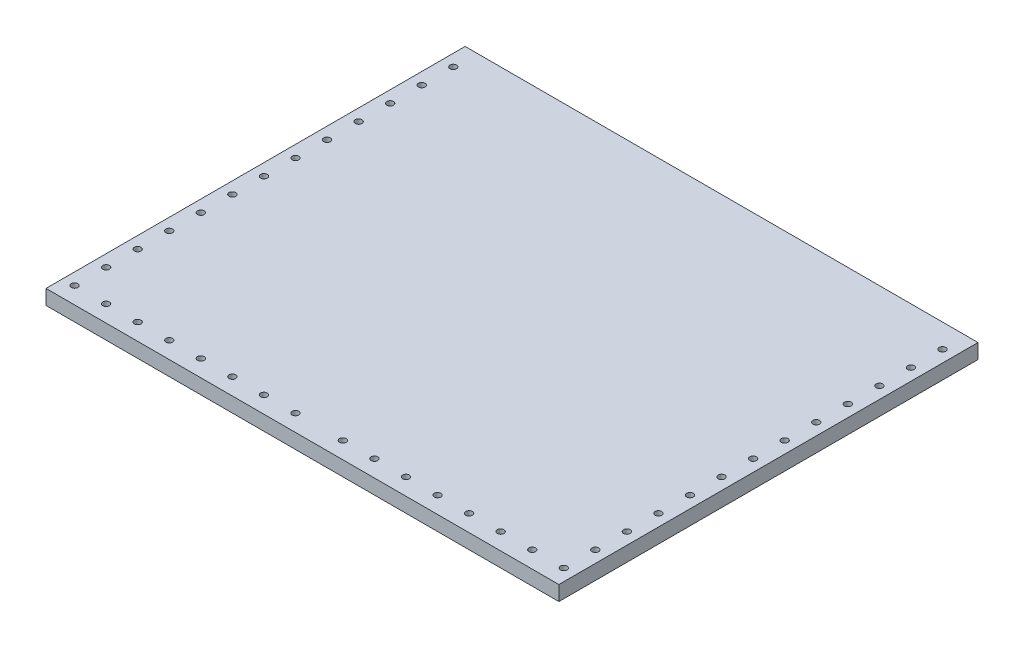
SolidWorks part; units mm, degrees
material "Teak"
ref_plane "Front Plane" through (0, 0, 0) normal (0, 0, 1) x (1, 0, 0)
ref_plane "Top Plane" through (0, 0, 0) normal (0, 1, 0) x (1, 0, 0)
ref_plane "Right Plane" through (0, 0, 0) normal (1, 0, 0) x (0, 0, -1)
sketch "Sketch1" plane through (0, 0, 0) normal (0, 1, 0) x (1, 0, 0)
  line L1 (0, 0) -> (412.75, 0)
  line L2 (0, 0) -> (0, 584.2)
  line L3 (0, 584.2) -> (412.75, 584.2)
  line L4 (412.75, 0) -> (412.75, 584.2)
  dimension "D1" = 584.2
  dimension "D2" = 412.75
extrude "Boss-Extrude1" add sketch "Sketch1" along normal blind 11.9062
sketch "Sketch2" plane through (0, 11.9062, 0) normal (0, 1, 0) x (1, 0, 0)
  line L0 (0, 584.2) -> (0, 0) construction
  line L1 (0, 477.012) -> (40.64, 477.012)
  line L2 (0, 477.012) -> (0, 337.312)
  line L3 (0, 337.312) -> (40.64, 337.312)
  line L4 (40.64, 477.012) -> (40.64, 337.312)
  line L5 (206.375, 0) -> (206.375, 59.5989)
  line L7 (0, 0) -> (412.75, 0) construction
  line L8 (372.11, 477.012) -> (372.11, 337.312)
  line L9 (412.75, 337.312) -> (372.11, 337.312)
  line L10 (412.75, 477.012) -> (412.75, 337.312)
  line L11 (412.75, 477.012) -> (372.11, 477.012)
  line M5 (0, 584.2) -> (0, 0)
  line M7 (412.75, 0) -> (412.75, 584.2)
  dimension "D1" = 139.7
  dimension "D2" = 40.64
extrude "Cut-Extrude1" cut sketch "Sketch2" against normal through all contours L4 L1 L3 M5 | L11 L8 L9 M7 region at (20.32, 11.9062, -407.162) region at (392.43, 11.9062, -407.162)
sketch "Sketch3" plane through (0, 11.9062, 0) normal (0, 1, 0) x (1, 0, 0)
  line L0 (0, 337.312) -> (0, 0) construction
  line L1 (0, 0) -> (412.75, 0) construction
  circle A0 centre (9.525, 13.462) radius 2.667
  circle A2 centre (34.925, 13.462) radius 2.667
  circle A4 centre (60.325, 13.462) radius 2.667
  circle A6 centre (85.725, 13.462) radius 2.667
  circle A8 centre (111.125, 13.462) radius 2.667
  circle A10 centre (136.525, 13.462) radius 2.667
  circle A12 centre (161.925, 13.462) radius 2.667
  circle A14 centre (187.325, 13.462) radius 2.667
  circle A17 centre (225.425, 13.462) radius 2.667
  circle A19 centre (250.825, 13.462) radius 2.667
  circle A21 centre (276.225, 13.462) radius 2.667
  circle A23 centre (301.625, 13.462) radius 2.667
  circle A25 centre (327.025, 13.462) radius 2.667
  circle A27 centre (352.425, 13.462) radius 2.667
  circle A29 centre (377.825, 13.462) radius 2.667
  circle A31 centre (403.225, 13.462) radius 2.667
  circle A62 centre (403.225, 38.862) radius 2.667
  circle A93 centre (403.225, 64.262) radius 2.667
  circle A124 centre (403.225, 89.662) radius 2.667
  circle A155 centre (403.225, 115.062) radius 2.667
  circle A186 centre (403.225, 140.462) radius 2.667
  circle A217 centre (403.225, 165.862) radius 2.667
  circle A248 centre (403.225, 191.262) radius 2.667
  circle A279 centre (403.225, 216.662) radius 2.667
  circle A310 centre (403.225, 242.062) radius 2.667
  circle A341 centre (403.225, 267.462) radius 2.667
  circle A372 centre (403.225, 292.862) radius 2.667
  circle A403 centre (403.225, 318.262) radius 2.667
  circle A434 centre (403.225, 343.662) radius 2.667
  circle A465 centre (403.225, 369.062) radius 2.667
  circle A496 centre (403.225, 394.462) radius 2.667
  circle A527 centre (403.225, 419.862) radius 2.667
  circle A558 centre (403.225, 445.262) radius 2.667
  circle A589 centre (403.225, 470.662) radius 2.667
  circle A620 centre (403.225, 496.062) radius 2.667
  circle A651 centre (403.225, 521.462) radius 2.667
  circle A682 centre (403.225, 546.862) radius 2.667
  circle A713 centre (403.225, 572.262) radius 2.667
  circle A714 centre (9.525, 38.862) radius 2.667
  circle A715 centre (9.525, 64.262) radius 2.667
  circle A716 centre (9.525, 89.662) radius 2.667
  circle A717 centre (9.525, 115.062) radius 2.667
  circle A718 centre (9.525, 140.462) radius 2.667
  circle A719 centre (9.525, 165.862) radius 2.667
  circle A720 centre (9.525, 191.262) radius 2.667
  circle A721 centre (9.525, 216.662) radius 2.667
  circle A722 centre (9.525, 242.062) radius 2.667
  circle A723 centre (9.525, 267.462) radius 2.667
  circle A724 centre (9.525, 292.862) radius 2.667
  circle A725 centre (9.525, 318.262) radius 2.667
  circle A726 centre (9.525, 343.662) radius 2.667
  circle A727 centre (9.525, 369.062) radius 2.667
  circle A728 centre (9.525, 394.462) radius 2.667
  circle A729 centre (9.525, 419.862) radius 2.667
  circle A730 centre (9.525, 445.262) radius 2.667
  circle A731 centre (9.525, 470.662) radius 2.667
  circle A732 centre (9.525, 496.062) radius 2.667
  circle A733 centre (9.525, 521.462) radius 2.667
  circle A734 centre (9.525, 546.862) radius 2.667
  circle A735 centre (9.525, 572.262) radius 2.667
  circle A736 centre (34.925, 38.862) radius 2.667 [skipped]
  circle A737 centre (47.625, 38.862) radius 2.667 [skipped]
  circle A738 centre (60.325, 38.862) radius 2.667 [skipped]
  circle A739 centre (73.025, 38.862) radius 2.667 [skipped]
  circle A740 centre (85.725, 38.862) radius 2.667 [skipped]
  circle A741 centre (98.425, 38.862) radius 2.667 [skipped]
  circle A742 centre (111.125, 38.862) radius 2.667 [skipped]
  circle A743 centre (123.825, 38.862) radius 2.667 [skipped]
  circle A744 centre (136.525, 38.862) radius 2.667 [skipped]
  circle A745 centre (149.225, 38.862) radius 2.667 [skipped]
  circle A746 centre (161.925, 38.862) radius 2.667 [skipped]
  circle A747 centre (174.625, 38.862) radius 2.667 [skipped]
  circle A748 centre (187.325, 38.862) radius 2.667 [skipped]
  circle A749 centre (200.025, 38.862) radius 2.667 [skipped]
  circle A750 centre (212.725, 38.862) radius 2.667 [skipped]
  circle A751 centre (225.425, 38.862) radius 2.667 [skipped]
  circle A752 centre (238.125, 38.862) radius 2.667 [skipped]
  circle A753 centre (250.825, 38.862) radius 2.667 [skipped]
  circle A754 centre (263.525, 38.862) radius 2.667 [skipped]
  circle A755 centre (276.225, 38.862) radius 2.667 [skipped]
  circle A756 centre (288.925, 38.862) radius 2.667 [skipped]
  circle A757 centre (301.625, 38.862) radius 2.667 [skipped]
  circle A758 centre (314.325, 38.862) radius 2.667 [skipped]
  circle A759 centre (327.025, 38.862) radius 2.667 [skipped]
  circle A760 centre (339.725, 38.862) radius 2.667 [skipped]
  circle A761 centre (352.425, 38.862) radius 2.667 [skipped]
  circle A762 centre (365.125, 38.862) radius 2.667 [skipped]
  circle A763 centre (377.825, 38.862) radius 2.667 [skipped]
  circle A764 centre (390.525, 38.862) radius 2.667 [skipped]
  circle A765 centre (34.925, 64.262) radius 2.667 [skipped]
  circle A766 centre (47.625, 64.262) radius 2.667 [skipped]
  circle A767 centre (60.325, 64.262) radius 2.667 [skipped]
  circle A768 centre (73.025, 64.262) radius 2.667 [skipped]
  circle A769 centre (85.725, 64.262) radius 2.667 [skipped]
  circle A770 centre (98.425, 64.262) radius 2.667 [skipped]
  circle A771 centre (111.125, 64.262) radius 2.667 [skipped]
  circle A772 centre (123.825, 64.262) radius 2.667 [skipped]
  circle A773 centre (136.525, 64.262) radius 2.667 [skipped]
  circle A774 centre (149.225, 64.262) radius 2.667 [skipped]
  circle A775 centre (161.925, 64.262) radius 2.667 [skipped]
  circle A776 centre (174.625, 64.262) radius 2.667 [skipped]
  circle A777 centre (187.325, 64.262) radius 2.667 [skipped]
  circle A778 centre (200.025, 64.262) radius 2.667 [skipped]
  circle A779 centre (212.725, 64.262) radius 2.667 [skipped]
  circle A780 centre (225.425, 64.262) radius 2.667 [skipped]
  circle A781 centre (238.125, 64.262) radius 2.667 [skipped]
  circle A782 centre (250.825, 64.262) radius 2.667 [skipped]
  circle A783 centre (263.525, 64.262) radius 2.667 [skipped]
  circle A784 centre (276.225, 64.262) radius 2.667 [skipped]
  circle A785 centre (288.925, 64.262) radius 2.667 [skipped]
  circle A786 centre (301.625, 64.262) radius 2.667 [skipped]
  circle A787 centre (314.325, 64.262) radius 2.667 [skipped]
  circle A788 centre (327.025, 64.262) radius 2.667 [skipped]
  circle A789 centre (339.725, 64.262) radius 2.667 [skipped]
  circle A790 centre (352.425, 64.262) radius 2.667 [skipped]
  circle A791 centre (365.125, 64.262) radius 2.667 [skipped]
  circle A792 centre (377.825, 64.262) radius 2.667 [skipped]
  circle A793 centre (390.525, 64.262) radius 2.667 [skipped]
  circle A794 centre (34.925, 89.662) radius 2.667 [skipped]
  circle A795 centre (47.625, 89.662) radius 2.667 [skipped]
  circle A796 centre (60.325, 89.662) radius 2.667 [skipped]
  circle A797 centre (73.025, 89.662) radius 2.667 [skipped]
  circle A798 centre (85.725, 89.662) radius 2.667 [skipped]
  circle A799 centre (98.425, 89.662) radius 2.667 [skipped]
  circle A800 centre (111.125, 89.662) radius 2.667 [skipped]
  circle A801 centre (123.825, 89.662) radius 2.667 [skipped]
  circle A802 centre (136.525, 89.662) radius 2.667 [skipped]
  circle A803 centre (149.225, 89.662) radius 2.667 [skipped]
  circle A804 centre (161.925, 89.662) radius 2.667 [skipped]
  circle A805 centre (174.625, 89.662) radius 2.667 [skipped]
  circle A806 centre (187.325, 89.662) radius 2.667 [skipped]
  circle A807 centre (200.025, 89.662) radius 2.667 [skipped]
  circle A808 centre (212.725, 89.662) radius 2.667 [skipped]
  circle A809 centre (225.425, 89.662) radius 2.667 [skipped]
  circle A810 centre (238.125, 89.662) radius 2.667 [skipped]
  circle A811 centre (250.825, 89.662) radius 2.667 [skipped]
  circle A812 centre (263.525, 89.662) radius 2.667 [skipped]
  circle A813 centre (276.225, 89.662) radius 2.667 [skipped]
  circle A814 centre (288.925, 89.662) radius 2.667 [skipped]
  circle A815 centre (301.625, 89.662) radius 2.667 [skipped]
  circle A816 centre (314.325, 89.662) radius 2.667 [skipped]
  circle A817 centre (327.025, 89.662) radius 2.667 [skipped]
  circle A818 centre (339.725, 89.662) radius 2.667 [skipped]
  circle A819 centre (352.425, 89.662) radius 2.667 [skipped]
  circle A820 centre (365.125, 89.662) radius 2.667 [skipped]
  circle A821 centre (377.825, 89.662) radius 2.667 [skipped]
  circle A822 centre (390.525, 89.662) radius 2.667 [skipped]
  circle A823 centre (34.925, 115.062) radius 2.667 [skipped]
  circle A824 centre (47.625, 115.062) radius 2.667 [skipped]
  circle A825 centre (60.325, 115.062) radius 2.667 [skipped]
  circle A826 centre (73.025, 115.062) radius 2.667 [skipped]
  circle A827 centre (85.725, 115.062) radius 2.667 [skipped]
  circle A828 centre (98.425, 115.062) radius 2.667 [skipped]
  circle A829 centre (111.125, 115.062) radius 2.667 [skipped]
  circle A830 centre (123.825, 115.062) radius 2.667 [skipped]
  circle A831 centre (136.525, 115.062) radius 2.667 [skipped]
  circle A832 centre (149.225, 115.062) radius 2.667 [skipped]
  circle A833 centre (161.925, 115.062) radius 2.667 [skipped]
  circle A834 centre (174.625, 115.062) radius 2.667 [skipped]
  circle A835 centre (187.325, 115.062) radius 2.667 [skipped]
  circle A836 centre (200.025, 115.062) radius 2.667 [skipped]
  circle A837 centre (212.725, 115.062) radius 2.667 [skipped]
  circle A838 centre (225.425, 115.062) radius 2.667 [skipped]
  circle A839 centre (238.125, 115.062) radius 2.667 [skipped]
  circle A840 centre (250.825, 115.062) radius 2.667 [skipped]
  circle A841 centre (263.525, 115.062) radius 2.667 [skipped]
  circle A842 centre (276.225, 115.062) radius 2.667 [skipped]
  circle A843 centre (288.925, 115.062) radius 2.667 [skipped]
  circle A844 centre (301.625, 115.062) radius 2.667 [skipped]
  circle A845 centre (314.325, 115.062) radius 2.667 [skipped]
  circle A846 centre (327.025, 115.062) radius 2.667 [skipped]
  circle A847 centre (339.725, 115.062) radius 2.667 [skipped]
  circle A848 centre (352.425, 115.062) radius 2.667 [skipped]
  circle A849 centre (365.125, 115.062) radius 2.667 [skipped]
  circle A850 centre (377.825, 115.062) radius 2.667 [skipped]
  circle A851 centre (390.525, 115.062) radius 2.667 [skipped]
  circle A852 centre (34.925, 140.462) radius 2.667 [skipped]
  circle A853 centre (47.625, 140.462) radius 2.667 [skipped]
  circle A854 centre (60.325, 140.462) radius 2.667 [skipped]
  circle A855 centre (73.025, 140.462) radius 2.667 [skipped]
  circle A856 centre (85.725, 140.462) radius 2.667 [skipped]
  circle A857 centre (98.425, 140.462) radius 2.667 [skipped]
  circle A858 centre (111.125, 140.462) radius 2.667 [skipped]
  circle A859 centre (123.825, 140.462) radius 2.667 [skipped]
  circle A860 centre (136.525, 140.462) radius 2.667 [skipped]
  circle A861 centre (149.225, 140.462) radius 2.667 [skipped]
  circle A862 centre (161.925, 140.462) radius 2.667 [skipped]
  circle A863 centre (174.625, 140.462) radius 2.667 [skipped]
  circle A864 centre (187.325, 140.462) radius 2.667 [skipped]
  circle A865 centre (200.025, 140.462) radius 2.667 [skipped]
  circle A866 centre (212.725, 140.462) radius 2.667 [skipped]
  circle A867 centre (225.425, 140.462) radius 2.667 [skipped]
  circle A868 centre (238.125, 140.462) radius 2.667 [skipped]
  circle A869 centre (250.825, 140.462) radius 2.667 [skipped]
  circle A870 centre (263.525, 140.462) radius 2.667 [skipped]
  circle A871 centre (276.225, 140.462) radius 2.667 [skipped]
  circle A872 centre (288.925, 140.462) radius 2.667 [skipped]
  circle A873 centre (301.625, 140.462) radius 2.667 [skipped]
  circle A874 centre (314.325, 140.462) radius 2.667 [skipped]
  circle A875 centre (327.025, 140.462) radius 2.667 [skipped]
  circle A876 centre (339.725, 140.462) radius 2.667 [skipped]
  circle A877 centre (352.425, 140.462) radius 2.667 [skipped]
  circle A878 centre (365.125, 140.462) radius 2.667 [skipped]
  circle A879 centre (377.825, 140.462) radius 2.667 [skipped]
  circle A880 centre (390.525, 140.462) radius 2.667 [skipped]
  circle A881 centre (34.925, 165.862) radius 2.667 [skipped]
  circle A882 centre (47.625, 165.862) radius 2.667 [skipped]
  circle A883 centre (60.325, 165.862) radius 2.667 [skipped]
  circle A884 centre (73.025, 165.862) radius 2.667 [skipped]
  circle A885 centre (85.725, 165.862) radius 2.667 [skipped]
  circle A886 centre (98.425, 165.862) radius 2.667 [skipped]
  circle A887 centre (111.125, 165.862) radius 2.667 [skipped]
  circle A888 centre (123.825, 165.862) radius 2.667 [skipped]
  circle A889 centre (136.525, 165.862) radius 2.667 [skipped]
  circle A890 centre (149.225, 165.862) radius 2.667 [skipped]
  circle A891 centre (161.925, 165.862) radius 2.667 [skipped]
  circle A892 centre (174.625, 165.862) radius 2.667 [skipped]
  circle A893 centre (187.325, 165.862) radius 2.667 [skipped]
  circle A894 centre (200.025, 165.862) radius 2.667 [skipped]
  circle A895 centre (212.725, 165.862) radius 2.667 [skipped]
  circle A896 centre (225.425, 165.862) radius 2.667 [skipped]
  circle A897 centre (238.125, 165.862) radius 2.667 [skipped]
  circle A898 centre (250.825, 165.862) radius 2.667 [skipped]
  circle A899 centre (263.525, 165.862) radius 2.667 [skipped]
  circle A900 centre (276.225, 165.862) radius 2.667 [skipped]
  circle A901 centre (288.925, 165.862) radius 2.667 [skipped]
  circle A902 centre (301.625, 165.862) radius 2.667 [skipped]
  circle A903 centre (314.325, 165.862) radius 2.667 [skipped]
  circle A904 centre (327.025, 165.862) radius 2.667 [skipped]
  circle A905 centre (339.725, 165.862) radius 2.667 [skipped]
  circle A906 centre (352.425, 165.862) radius 2.667 [skipped]
  circle A907 centre (365.125, 165.862) radius 2.667 [skipped]
  circle A908 centre (377.825, 165.862) radius 2.667 [skipped]
  circle A909 centre (390.525, 165.862) radius 2.667 [skipped]
  circle A910 centre (34.925, 191.262) radius 2.667 [skipped]
  circle A911 centre (47.625, 191.262) radius 2.667 [skipped]
  circle A912 centre (60.325, 191.262) radius 2.667 [skipped]
  circle A913 centre (73.025, 191.262) radius 2.667 [skipped]
  circle A914 centre (85.725, 191.262) radius 2.667 [skipped]
  circle A915 centre (98.425, 191.262) radius 2.667 [skipped]
  circle A916 centre (111.125, 191.262) radius 2.667 [skipped]
  circle A917 centre (123.825, 191.262) radius 2.667 [skipped]
  circle A918 centre (136.525, 191.262) radius 2.667 [skipped]
  circle A919 centre (149.225, 191.262) radius 2.667 [skipped]
  circle A920 centre (161.925, 191.262) radius 2.667 [skipped]
  circle A921 centre (174.625, 191.262) radius 2.667 [skipped]
  circle A922 centre (187.325, 191.262) radius 2.667 [skipped]
  circle A923 centre (200.025, 191.262) radius 2.667 [skipped]
  circle A924 centre (212.725, 191.262) radius 2.667 [skipped]
  circle A925 centre (225.425, 191.262) radius 2.667 [skipped]
  circle A926 centre (238.125, 191.262) radius 2.667 [skipped]
  circle A927 centre (250.825, 191.262) radius 2.667 [skipped]
  circle A928 centre (263.525, 191.262) radius 2.667 [skipped]
  circle A929 centre (276.225, 191.262) radius 2.667 [skipped]
  circle A930 centre (288.925, 191.262) radius 2.667 [skipped]
  circle A931 centre (301.625, 191.262) radius 2.667 [skipped]
  circle A932 centre (314.325, 191.262) radius 2.667 [skipped]
  circle A933 centre (327.025, 191.262) radius 2.667 [skipped]
  circle A934 centre (339.725, 191.262) radius 2.667 [skipped]
  circle A935 centre (352.425, 191.262) radius 2.667 [skipped]
  circle A936 centre (365.125, 191.262) radius 2.667 [skipped]
  circle A937 centre (377.825, 191.262) radius 2.667 [skipped]
  circle A938 centre (390.525, 191.262) radius 2.667 [skipped]
  circle A939 centre (34.925, 216.662) radius 2.667 [skipped]
  circle A940 centre (47.625, 216.662) radius 2.667 [skipped]
  circle A941 centre (60.325, 216.662) radius 2.667 [skipped]
  circle A942 centre (73.025, 216.662) radius 2.667 [skipped]
  circle A943 centre (85.725, 216.662) radius 2.667 [skipped]
  circle A944 centre (98.425, 216.662) radius 2.667 [skipped]
  circle A945 centre (111.125, 216.662) radius 2.667 [skipped]
  circle A946 centre (123.825, 216.662) radius 2.667 [skipped]
  circle A947 centre (136.525, 216.662) radius 2.667 [skipped]
  circle A948 centre (149.225, 216.662) radius 2.667 [skipped]
  circle A949 centre (161.925, 216.662) radius 2.667 [skipped]
  circle A950 centre (174.625, 216.662) radius 2.667 [skipped]
  circle A951 centre (187.325, 216.662) radius 2.667 [skipped]
  circle A952 centre (200.025, 216.662) radius 2.667 [skipped]
  circle A953 centre (212.725, 216.662) radius 2.667 [skipped]
  circle A954 centre (225.425, 216.662) radius 2.667 [skipped]
  circle A955 centre (238.125, 216.662) radius 2.667 [skipped]
  circle A956 centre (250.825, 216.662) radius 2.667 [skipped]
  circle A957 centre (263.525, 216.662) radius 2.667 [skipped]
  circle A958 centre (276.225, 216.662) radius 2.667 [skipped]
  circle A959 centre (288.925, 216.662) radius 2.667 [skipped]
  circle A960 centre (301.625, 216.662) radius 2.667 [skipped]
  circle A961 centre (314.325, 216.662) radius 2.667 [skipped]
  circle A962 centre (327.025, 216.662) radius 2.667 [skipped]
  circle A963 centre (339.725, 216.662) radius 2.667 [skipped]
  circle A964 centre (352.425, 216.662) radius 2.667 [skipped]
  circle A965 centre (365.125, 216.662) radius 2.667 [skipped]
  circle A966 centre (377.825, 216.662) radius 2.667 [skipped]
  circle A967 centre (390.525, 216.662) radius 2.667 [skipped]
  circle A968 centre (34.925, 242.062) radius 2.667 [skipped]
  circle A969 centre (47.625, 242.062) radius 2.667 [skipped]
  circle A970 centre (60.325, 242.062) radius 2.667 [skipped]
  circle A971 centre (73.025, 242.062) radius 2.667 [skipped]
  circle A972 centre (85.725, 242.062) radius 2.667 [skipped]
  circle A973 centre (98.425, 242.062) radius 2.667 [skipped]
  circle A974 centre (111.125, 242.062) radius 2.667 [skipped]
  circle A975 centre (123.825, 242.062) radius 2.667 [skipped]
  circle A976 centre (136.525, 242.062) radius 2.667 [skipped]
  circle A977 centre (149.225, 242.062) radius 2.667 [skipped]
  circle A978 centre (161.925, 242.062) radius 2.667 [skipped]
  circle A979 centre (174.625, 242.062) radius 2.667 [skipped]
  circle A980 centre (187.325, 242.062) radius 2.667 [skipped]
  circle A981 centre (200.025, 242.062) radius 2.667 [skipped]
  circle A982 centre (212.725, 242.062) radius 2.667 [skipped]
  circle A983 centre (225.425, 242.062) radius 2.667 [skipped]
  circle A984 centre (238.125, 242.062) radius 2.667 [skipped]
  circle A985 centre (250.825, 242.062) radius 2.667 [skipped]
  circle A986 centre (263.525, 242.062) radius 2.667 [skipped]
  circle A987 centre (276.225, 242.062) radius 2.667 [skipped]
  circle A988 centre (288.925, 242.062) radius 2.667 [skipped]
  circle A989 centre (301.625, 242.062) radius 2.667 [skipped]
  circle A990 centre (314.325, 242.062) radius 2.667 [skipped]
  circle A991 centre (327.025, 242.062) radius 2.667 [skipped]
  circle A992 centre (339.725, 242.062) radius 2.667 [skipped]
  circle A993 centre (352.425, 242.062) radius 2.667 [skipped]
  circle A994 centre (365.125, 242.062) radius 2.667 [skipped]
  circle A995 centre (377.825, 242.062) radius 2.667 [skipped]
  circle A996 centre (390.525, 242.062) radius 2.667 [skipped]
  circle A997 centre (34.925, 267.462) radius 2.667 [skipped]
  circle A998 centre (47.625, 267.462) radius 2.667 [skipped]
  circle A999 centre (60.325, 267.462) radius 2.667 [skipped]
  circle A1000 centre (73.025, 267.462) radius 2.667 [skipped]
  circle A1001 centre (85.725, 267.462) radius 2.667 [skipped]
  circle A1002 centre (98.425, 267.462) radius 2.667 [skipped]
  circle A1003 centre (111.125, 267.462) radius 2.667 [skipped]
  circle A1004 centre (123.825, 267.462) radius 2.667 [skipped]
  circle A1005 centre (136.525, 267.462) radius 2.667 [skipped]
  circle A1006 centre (149.225, 267.462) radius 2.667 [skipped]
  circle A1007 centre (161.925, 267.462) radius 2.667 [skipped]
  circle A1008 centre (174.625, 267.462) radius 2.667 [skipped]
  circle A1009 centre (187.325, 267.462) radius 2.667 [skipped]
  circle A1010 centre (200.025, 267.462) radius 2.667 [skipped]
  circle A1011 centre (212.725, 267.462) radius 2.667 [skipped]
  circle A1012 centre (225.425, 267.462) radius 2.667 [skipped]
  circle A1013 centre (238.125, 267.462) radius 2.667 [skipped]
  circle A1014 centre (250.825, 267.462) radius 2.667 [skipped]
  circle A1015 centre (263.525, 267.462) radius 2.667 [skipped]
  circle A1016 centre (276.225, 267.462) radius 2.667 [skipped]
  circle A1017 centre (288.925, 267.462) radius 2.667 [skipped]
  circle A1018 centre (301.625, 267.462) radius 2.667 [skipped]
  circle A1019 centre (314.325, 267.462) radius 2.667 [skipped]
  circle A1020 centre (327.025, 267.462) radius 2.667 [skipped]
  circle A1021 centre (339.725, 267.462) radius 2.667 [skipped]
  circle A1022 centre (352.425, 267.462) radius 2.667 [skipped]
  circle A1023 centre (365.125, 267.462) radius 2.667 [skipped]
  circle A1024 centre (377.825, 267.462) radius 2.667 [skipped]
  circle A1025 centre (390.525, 267.462) radius 2.667 [skipped]
  circle A1026 centre (34.925, 292.862) radius 2.667 [skipped]
  circle A1027 centre (47.625, 292.862) radius 2.667 [skipped]
  circle A1028 centre (60.325, 292.862) radius 2.667 [skipped]
  circle A1029 centre (73.025, 292.862) radius 2.667 [skipped]
  circle A1030 centre (85.725, 292.862) radius 2.667 [skipped]
  circle A1031 centre (98.425, 292.862) radius 2.667 [skipped]
  circle A1032 centre (111.125, 292.862) radius 2.667 [skipped]
  circle A1033 centre (123.825, 292.862) radius 2.667 [skipped]
  circle A1034 centre (136.525, 292.862) radius 2.667 [skipped]
  circle A1035 centre (149.225, 292.862) radius 2.667 [skipped]
  circle A1036 centre (161.925, 292.862) radius 2.667 [skipped]
  circle A1037 centre (174.625, 292.862) radius 2.667 [skipped]
  circle A1038 centre (187.325, 292.862) radius 2.667 [skipped]
  circle A1039 centre (200.025, 292.862) radius 2.667 [skipped]
  circle A1040 centre (212.725, 292.862) radius 2.667 [skipped]
  circle A1041 centre (225.425, 292.862) radius 2.667 [skipped]
  circle A1042 centre (238.125, 292.862) radius 2.667 [skipped]
  circle A1043 centre (250.825, 292.862) radius 2.667 [skipped]
  circle A1044 centre (263.525, 292.862) radius 2.667 [skipped]
  circle A1045 centre (276.225, 292.862) radius 2.667 [skipped]
  circle A1046 centre (288.925, 292.862) radius 2.667 [skipped]
  circle A1047 centre (301.625, 292.862) radius 2.667 [skipped]
  circle A1048 centre (314.325, 292.862) radius 2.667 [skipped]
  circle A1049 centre (327.025, 292.862) radius 2.667 [skipped]
  circle A1050 centre (339.725, 292.862) radius 2.667 [skipped]
  circle A1051 centre (352.425, 292.862) radius 2.667 [skipped]
  circle A1052 centre (365.125, 292.862) radius 2.667 [skipped]
  circle A1053 centre (377.825, 292.862) radius 2.667 [skipped]
  circle A1054 centre (390.525, 292.862) radius 2.667 [skipped]
  circle A1055 centre (34.925, 318.262) radius 2.667 [skipped]
  circle A1056 centre (47.625, 318.262) radius 2.667 [skipped]
  circle A1057 centre (60.325, 318.262) radius 2.667 [skipped]
  circle A1058 centre (73.025, 318.262) radius 2.667 [skipped]
  circle A1059 centre (85.725, 318.262) radius 2.667 [skipped]
  circle A1060 centre (98.425, 318.262) radius 2.667 [skipped]
  circle A1061 centre (111.125, 318.262) radius 2.667 [skipped]
  circle A1062 centre (123.825, 318.262) radius 2.667 [skipped]
  circle A1063 centre (136.525, 318.262) radius 2.667 [skipped]
  circle A1064 centre (149.225, 318.262) radius 2.667 [skipped]
  circle A1065 centre (161.925, 318.262) radius 2.667 [skipped]
  circle A1066 centre (174.625, 318.262) radius 2.667 [skipped]
  circle A1067 centre (187.325, 318.262) radius 2.667 [skipped]
  circle A1068 centre (200.025, 318.262) radius 2.667 [skipped]
  circle A1069 centre (212.725, 318.262) radius 2.667 [skipped]
  circle A1070 centre (225.425, 318.262) radius 2.667 [skipped]
  circle A1071 centre (238.125, 318.262) radius 2.667 [skipped]
  circle A1072 centre (250.825, 318.262) radius 2.667 [skipped]
  circle A1073 centre (263.525, 318.262) radius 2.667 [skipped]
  circle A1074 centre (276.225, 318.262) radius 2.667 [skipped]
  circle A1075 centre (288.925, 318.262) radius 2.667 [skipped]
  circle A1076 centre (301.625, 318.262) radius 2.667 [skipped]
  circle A1077 centre (314.325, 318.262) radius 2.667 [skipped]
  circle A1078 centre (327.025, 318.262) radius 2.667 [skipped]
  circle A1079 centre (339.725, 318.262) radius 2.667 [skipped]
  circle A1080 centre (352.425, 318.262) radius 2.667 [skipped]
  circle A1081 centre (365.125, 318.262) radius 2.667 [skipped]
  circle A1082 centre (377.825, 318.262) radius 2.667 [skipped]
  circle A1083 centre (390.525, 318.262) radius 2.667 [skipped]
  circle A1084 centre (34.925, 343.662) radius 2.667 [skipped]
  circle A1085 centre (47.625, 343.662) radius 2.667 [skipped]
  circle A1086 centre (60.325, 343.662) radius 2.667 [skipped]
  circle A1087 centre (73.025, 343.662) radius 2.667 [skipped]
  circle A1088 centre (85.725, 343.662) radius 2.667 [skipped]
  circle A1089 centre (98.425, 343.662) radius 2.667 [skipped]
  circle A1090 centre (111.125, 343.662) radius 2.667 [skipped]
  circle A1091 centre (123.825, 343.662) radius 2.667 [skipped]
  circle A1092 centre (136.525, 343.662) radius 2.667 [skipped]
  circle A1093 centre (149.225, 343.662) radius 2.667 [skipped]
  circle A1094 centre (161.925, 343.662) radius 2.667 [skipped]
  circle A1095 centre (174.625, 343.662) radius 2.667 [skipped]
  circle A1096 centre (187.325, 343.662) radius 2.667 [skipped]
  circle A1097 centre (200.025, 343.662) radius 2.667 [skipped]
  circle A1098 centre (212.725, 343.662) radius 2.667 [skipped]
  circle A1099 centre (225.425, 343.662) radius 2.667 [skipped]
  circle A1100 centre (238.125, 343.662) radius 2.667 [skipped]
  circle A1101 centre (250.825, 343.662) radius 2.667 [skipped]
  circle A1102 centre (263.525, 343.662) radius 2.667 [skipped]
  circle A1103 centre (276.225, 343.662) radius 2.667 [skipped]
  circle A1104 centre (288.925, 343.662) radius 2.667 [skipped]
  circle A1105 centre (301.625, 343.662) radius 2.667 [skipped]
  circle A1106 centre (314.325, 343.662) radius 2.667 [skipped]
  circle A1107 centre (327.025, 343.662) radius 2.667 [skipped]
  circle A1108 centre (339.725, 343.662) radius 2.667 [skipped]
  circle A1109 centre (352.425, 343.662) radius 2.667 [skipped]
  circle A1110 centre (365.125, 343.662) radius 2.667 [skipped]
  circle A1111 centre (377.825, 343.662) radius 2.667 [skipped]
  circle A1112 centre (390.525, 343.662) radius 2.667 [skipped]
  circle A1113 centre (34.925, 369.062) radius 2.667 [skipped]
  circle A1114 centre (47.625, 369.062) radius 2.667 [skipped]
  circle A1115 centre (60.325, 369.062) radius 2.667 [skipped]
  circle A1116 centre (73.025, 369.062) radius 2.667 [skipped]
  circle A1117 centre (85.725, 369.062) radius 2.667 [skipped]
  circle A1118 centre (98.425, 369.062) radius 2.667 [skipped]
  circle A1119 centre (111.125, 369.062) radius 2.667 [skipped]
  circle A1120 centre (123.825, 369.062) radius 2.667 [skipped]
  circle A1121 centre (136.525, 369.062) radius 2.667 [skipped]
  circle A1122 centre (149.225, 369.062) radius 2.667 [skipped]
  circle A1123 centre (161.925, 369.062) radius 2.667 [skipped]
  circle A1124 centre (174.625, 369.062) radius 2.667 [skipped]
  circle A1125 centre (187.325, 369.062) radius 2.667 [skipped]
  circle A1126 centre (200.025, 369.062) radius 2.667 [skipped]
  circle A1127 centre (212.725, 369.062) radius 2.667 [skipped]
  circle A1128 centre (225.425, 369.062) radius 2.667 [skipped]
  circle A1129 centre (238.125, 369.062) radius 2.667 [skipped]
  circle A1130 centre (250.825, 369.062) radius 2.667 [skipped]
  circle A1131 centre (263.525, 369.062) radius 2.667 [skipped]
  circle A1132 centre (276.225, 369.062) radius 2.667 [skipped]
  circle A1133 centre (288.925, 369.062) radius 2.667 [skipped]
  circle A1134 centre (301.625, 369.062) radius 2.667 [skipped]
  circle A1135 centre (314.325, 369.062) radius 2.667 [skipped]
  circle A1136 centre (327.025, 369.062) radius 2.667 [skipped]
  circle A1137 centre (339.725, 369.062) radius 2.667 [skipped]
  circle A1138 centre (352.425, 369.062) radius 2.667 [skipped]
  circle A1139 centre (365.125, 369.062) radius 2.667 [skipped]
  circle A1140 centre (377.825, 369.062) radius 2.667 [skipped]
  circle A1141 centre (390.525, 369.062) radius 2.667 [skipped]
  circle A1142 centre (34.925, 394.462) radius 2.667 [skipped]
  circle A1143 centre (47.625, 394.462) radius 2.667 [skipped]
  circle A1144 centre (60.325, 394.462) radius 2.667 [skipped]
  circle A1145 centre (73.025, 394.462) radius 2.667 [skipped]
  circle A1146 centre (85.725, 394.462) radius 2.667 [skipped]
  circle A1147 centre (98.425, 394.462) radius 2.667 [skipped]
  circle A1148 centre (111.125, 394.462) radius 2.667 [skipped]
  circle A1149 centre (123.825, 394.462) radius 2.667 [skipped]
  circle A1150 centre (136.525, 394.462) radius 2.667 [skipped]
  circle A1151 centre (149.225, 394.462) radius 2.667 [skipped]
  circle A1152 centre (161.925, 394.462) radius 2.667 [skipped]
  circle A1153 centre (174.625, 394.462) radius 2.667 [skipped]
  circle A1154 centre (187.325, 394.462) radius 2.667 [skipped]
  circle A1155 centre (200.025, 394.462) radius 2.667 [skipped]
  circle A1156 centre (212.725, 394.462) radius 2.667 [skipped]
  circle A1157 centre (225.425, 394.462) radius 2.667 [skipped]
  circle A1158 centre (238.125, 394.462) radius 2.667 [skipped]
  circle A1159 centre (250.825, 394.462) radius 2.667 [skipped]
  circle A1160 centre (263.525, 394.462) radius 2.667 [skipped]
  circle A1161 centre (276.225, 394.462) radius 2.667 [skipped]
  circle A1162 centre (288.925, 394.462) radius 2.667 [skipped]
  circle A1163 centre (301.625, 394.462) radius 2.667 [skipped]
  circle A1164 centre (314.325, 394.462) radius 2.667 [skipped]
  circle A1165 centre (327.025, 394.462) radius 2.667 [skipped]
  circle A1166 centre (339.725, 394.462) radius 2.667 [skipped]
  circle A1167 centre (352.425, 394.462) radius 2.667 [skipped]
  circle A1168 centre (365.125, 394.462) radius 2.667 [skipped]
  circle A1169 centre (377.825, 394.462) radius 2.667 [skipped]
  circle A1170 centre (390.525, 394.462) radius 2.667 [skipped]
  circle A1171 centre (34.925, 419.862) radius 2.667 [skipped]
  circle A1172 centre (47.625, 419.862) radius 2.667 [skipped]
  circle A1173 centre (60.325, 419.862) radius 2.667 [skipped]
  circle A1174 centre (73.025, 419.862) radius 2.667 [skipped]
  circle A1175 centre (85.725, 419.862) radius 2.667 [skipped]
  circle A1176 centre (98.425, 419.862) radius 2.667 [skipped]
  circle A1177 centre (111.125, 419.862) radius 2.667 [skipped]
  circle A1178 centre (123.825, 419.862) radius 2.667 [skipped]
  circle A1179 centre (136.525, 419.862) radius 2.667 [skipped]
  circle A1180 centre (149.225, 419.862) radius 2.667 [skipped]
  circle A1181 centre (161.925, 419.862) radius 2.667 [skipped]
  circle A1182 centre (174.625, 419.862) radius 2.667 [skipped]
  circle A1183 centre (187.325, 419.862) radius 2.667 [skipped]
  circle A1184 centre (200.025, 419.862) radius 2.667 [skipped]
  circle A1185 centre (212.725, 419.862) radius 2.667 [skipped]
  circle A1186 centre (225.425, 419.862) radius 2.667 [skipped]
  circle A1187 centre (238.125, 419.862) radius 2.667 [skipped]
  circle A1188 centre (250.825, 419.862) radius 2.667 [skipped]
  circle A1189 centre (263.525, 419.862) radius 2.667 [skipped]
  circle A1190 centre (276.225, 419.862) radius 2.667 [skipped]
  circle A1191 centre (288.925, 419.862) radius 2.667 [skipped]
  circle A1192 centre (301.625, 419.862) radius 2.667 [skipped]
  circle A1193 centre (314.325, 419.862) radius 2.667 [skipped]
  circle A1194 centre (327.025, 419.862) radius 2.667 [skipped]
  circle A1195 centre (339.725, 419.862) radius 2.667 [skipped]
  circle A1196 centre (352.425, 419.862) radius 2.667 [skipped]
  circle A1197 centre (365.125, 419.862) radius 2.667 [skipped]
  circle A1198 centre (377.825, 419.862) radius 2.667 [skipped]
  circle A1199 centre (390.525, 419.862) radius 2.667 [skipped]
  circle A1200 centre (34.925, 445.262) radius 2.667 [skipped]
  circle A1201 centre (47.625, 445.262) radius 2.667 [skipped]
  circle A1202 centre (60.325, 445.262) radius 2.667 [skipped]
  circle A1203 centre (73.025, 445.262) radius 2.667 [skipped]
  circle A1204 centre (85.725, 445.262) radius 2.667 [skipped]
  circle A1205 centre (98.425, 445.262) radius 2.667 [skipped]
  circle A1206 centre (111.125, 445.262) radius 2.667 [skipped]
  circle A1207 centre (123.825, 445.262) radius 2.667 [skipped]
  circle A1208 centre (136.525, 445.262) radius 2.667 [skipped]
  circle A1209 centre (149.225, 445.262) radius 2.667 [skipped]
  circle A1210 centre (161.925, 445.262) radius 2.667 [skipped]
  circle A1211 centre (174.625, 445.262) radius 2.667 [skipped]
  circle A1212 centre (187.325, 445.262) radius 2.667 [skipped]
  circle A1213 centre (200.025, 445.262) radius 2.667 [skipped]
  circle A1214 centre (212.725, 445.262) radius 2.667 [skipped]
  circle A1215 centre (225.425, 445.262) radius 2.667 [skipped]
  circle A1216 centre (238.125, 445.262) radius 2.667 [skipped]
  circle A1217 centre (250.825, 445.262) radius 2.667 [skipped]
  circle A1218 centre (263.525, 445.262) radius 2.667 [skipped]
  circle A1219 centre (276.225, 445.262) radius 2.667 [skipped]
  circle A1220 centre (288.925, 445.262) radius 2.667 [skipped]
  circle A1221 centre (301.625, 445.262) radius 2.667 [skipped]
  circle A1222 centre (314.325, 445.262) radius 2.667 [skipped]
  circle A1223 centre (327.025, 445.262) radius 2.667 [skipped]
  circle A1224 centre (339.725, 445.262) radius 2.667 [skipped]
  circle A1225 centre (352.425, 445.262) radius 2.667 [skipped]
  circle A1226 centre (365.125, 445.262) radius 2.667 [skipped]
  circle A1227 centre (377.825, 445.262) radius 2.667 [skipped]
  circle A1228 centre (390.525, 445.262) radius 2.667 [skipped]
  circle A1229 centre (34.925, 470.662) radius 2.667 [skipped]
  circle A1230 centre (47.625, 470.662) radius 2.667 [skipped]
  circle A1231 centre (60.325, 470.662) radius 2.667 [skipped]
  circle A1232 centre (73.025, 470.662) radius 2.667 [skipped]
  circle A1233 centre (85.725, 470.662) radius 2.667 [skipped]
  circle A1234 centre (98.425, 470.662) radius 2.667 [skipped]
  circle A1235 centre (111.125, 470.662) radius 2.667 [skipped]
  circle A1236 centre (123.825, 470.662) radius 2.667 [skipped]
  circle A1237 centre (136.525, 470.662) radius 2.667 [skipped]
  circle A1238 centre (149.225, 470.662) radius 2.667 [skipped]
  circle A1239 centre (161.925, 470.662) radius 2.667 [skipped]
  circle A1240 centre (174.625, 470.662) radius 2.667 [skipped]
  circle A1241 centre (187.325, 470.662) radius 2.667 [skipped]
  circle A1242 centre (200.025, 470.662) radius 2.667 [skipped]
  circle A1243 centre (212.725, 470.662) radius 2.667 [skipped]
  circle A1244 centre (225.425, 470.662) radius 2.667 [skipped]
  circle A1245 centre (238.125, 470.662) radius 2.667 [skipped]
  circle A1246 centre (250.825, 470.662) radius 2.667 [skipped]
  circle A1247 centre (263.525, 470.662) radius 2.667 [skipped]
  circle A1248 centre (276.225, 470.662) radius 2.667 [skipped]
  circle A1249 centre (288.925, 470.662) radius 2.667 [skipped]
  circle A1250 centre (301.625, 470.662) radius 2.667 [skipped]
  circle A1251 centre (314.325, 470.662) radius 2.667 [skipped]
  circle A1252 centre (327.025, 470.662) radius 2.667 [skipped]
  circle A1253 centre (339.725, 470.662) radius 2.667 [skipped]
  circle A1254 centre (352.425, 470.662) radius 2.667 [skipped]
  circle A1255 centre (365.125, 470.662) radius 2.667 [skipped]
  circle A1256 centre (377.825, 470.662) radius 2.667 [skipped]
  circle A1257 centre (390.525, 470.662) radius 2.667 [skipped]
  circle A1258 centre (34.925, 496.062) radius 2.667 [skipped]
  circle A1259 centre (47.625, 496.062) radius 2.667 [skipped]
  circle A1260 centre (60.325, 496.062) radius 2.667 [skipped]
  circle A1261 centre (73.025, 496.062) radius 2.667 [skipped]
  circle A1262 centre (85.725, 496.062) radius 2.667 [skipped]
  circle A1263 centre (98.425, 496.062) radius 2.667 [skipped]
  circle A1264 centre (111.125, 496.062) radius 2.667 [skipped]
  circle A1265 centre (123.825, 496.062) radius 2.667 [skipped]
  circle A1266 centre (136.525, 496.062) radius 2.667 [skipped]
  circle A1267 centre (149.225, 496.062) radius 2.667 [skipped]
  circle A1268 centre (161.925, 496.062) radius 2.667 [skipped]
  circle A1269 centre (174.625, 496.062) radius 2.667 [skipped]
  circle A1270 centre (187.325, 496.062) radius 2.667 [skipped]
  circle A1271 centre (200.025, 496.062) radius 2.667 [skipped]
  circle A1272 centre (212.725, 496.062) radius 2.667 [skipped]
  circle A1273 centre (225.425, 496.062) radius 2.667 [skipped]
  circle A1274 centre (238.125, 496.062) radius 2.667 [skipped]
  circle A1275 centre (250.825, 496.062) radius 2.667 [skipped]
  circle A1276 centre (263.525, 496.062) radius 2.667 [skipped]
  circle A1277 centre (276.225, 496.062) radius 2.667 [skipped]
  circle A1278 centre (288.925, 496.062) radius 2.667 [skipped]
  circle A1279 centre (301.625, 496.062) radius 2.667 [skipped]
  circle A1280 centre (314.325, 496.062) radius 2.667 [skipped]
  circle A1281 centre (327.025, 496.062) radius 2.667 [skipped]
  circle A1282 centre (339.725, 496.062) radius 2.667 [skipped]
  circle A1283 centre (352.425, 496.062) radius 2.667 [skipped]
  circle A1284 centre (365.125, 496.062) radius 2.667 [skipped]
  circle A1285 centre (377.825, 496.062) radius 2.667 [skipped]
  circle A1286 centre (390.525, 496.062) radius 2.667 [skipped]
  circle A1287 centre (34.925, 521.462) radius 2.667 [skipped]
  circle A1288 centre (47.625, 521.462) radius 2.667 [skipped]
  circle A1289 centre (60.325, 521.462) radius 2.667 [skipped]
  circle A1290 centre (73.025, 521.462) radius 2.667 [skipped]
  circle A1291 centre (85.725, 521.462) radius 2.667 [skipped]
  circle A1292 centre (98.425, 521.462) radius 2.667 [skipped]
  circle A1293 centre (111.125, 521.462) radius 2.667 [skipped]
  circle A1294 centre (123.825, 521.462) radius 2.667 [skipped]
  circle A1295 centre (136.525, 521.462) radius 2.667 [skipped]
  circle A1296 centre (149.225, 521.462) radius 2.667 [skipped]
  circle A1297 centre (161.925, 521.462) radius 2.667 [skipped]
  circle A1298 centre (174.625, 521.462) radius 2.667 [skipped]
  circle A1299 centre (187.325, 521.462) radius 2.667 [skipped]
  circle A1300 centre (200.025, 521.462) radius 2.667 [skipped]
  circle A1301 centre (212.725, 521.462) radius 2.667 [skipped]
  circle A1302 centre (225.425, 521.462) radius 2.667 [skipped]
  circle A1303 centre (238.125, 521.462) radius 2.667 [skipped]
  circle A1304 centre (250.825, 521.462) radius 2.667 [skipped]
  circle A1305 centre (263.525, 521.462) radius 2.667 [skipped]
  circle A1306 centre (276.225, 521.462) radius 2.667 [skipped]
  circle A1307 centre (288.925, 521.462) radius 2.667 [skipped]
  circle A1308 centre (301.625, 521.462) radius 2.667 [skipped]
  circle A1309 centre (314.325, 521.462) radius 2.667 [skipped]
  circle A1310 centre (327.025, 521.462) radius 2.667 [skipped]
  circle A1311 centre (339.725, 521.462) radius 2.667 [skipped]
  circle A1312 centre (352.425, 521.462) radius 2.667 [skipped]
  circle A1313 centre (365.125, 521.462) radius 2.667 [skipped]
  circle A1314 centre (377.825, 521.462) radius 2.667 [skipped]
  circle A1315 centre (390.525, 521.462) radius 2.667 [skipped]
  circle A1316 centre (34.925, 546.862) radius 2.667 [skipped]
  circle A1317 centre (47.625, 546.862) radius 2.667 [skipped]
  circle A1318 centre (60.325, 546.862) radius 2.667 [skipped]
  circle A1319 centre (73.025, 546.862) radius 2.667 [skipped]
  circle A1320 centre (85.725, 546.862) radius 2.667 [skipped]
  circle A1321 centre (98.425, 546.862) radius 2.667 [skipped]
  circle A1322 centre (111.125, 546.862) radius 2.667 [skipped]
  circle A1323 centre (123.825, 546.862) radius 2.667 [skipped]
  circle A1324 centre (136.525, 546.862) radius 2.667 [skipped]
  circle A1325 centre (149.225, 546.862) radius 2.667 [skipped]
  circle A1326 centre (161.925, 546.862) radius 2.667 [skipped]
  circle A1327 centre (174.625, 546.862) radius 2.667 [skipped]
  circle A1328 centre (187.325, 546.862) radius 2.667 [skipped]
  circle A1329 centre (200.025, 546.862) radius 2.667 [skipped]
  circle A1330 centre (212.725, 546.862) radius 2.667 [skipped]
  circle A1331 centre (225.425, 546.862) radius 2.667 [skipped]
  circle A1332 centre (238.125, 546.862) radius 2.667 [skipped]
  circle A1333 centre (250.825, 546.862) radius 2.667 [skipped]
  circle A1334 centre (263.525, 546.862) radius 2.667 [skipped]
  circle A1335 centre (276.225, 546.862) radius 2.667 [skipped]
  circle A1336 centre (288.925, 546.862) radius 2.667 [skipped]
  circle A1337 centre (301.625, 546.862) radius 2.667 [skipped]
  circle A1338 centre (314.325, 546.862) radius 2.667 [skipped]
  circle A1339 centre (327.025, 546.862) radius 2.667 [skipped]
  circle A1340 centre (339.725, 546.862) radius 2.667 [skipped]
  circle A1341 centre (352.425, 546.862) radius 2.667 [skipped]
  circle A1342 centre (365.125, 546.862) radius 2.667 [skipped]
  circle A1343 centre (377.825, 546.862) radius 2.667 [skipped]
  circle A1344 centre (390.525, 546.862) radius 2.667 [skipped]
  circle A1345 centre (34.925, 572.262) radius 2.667 [skipped]
  circle A1346 centre (47.625, 572.262) radius 2.667 [skipped]
  circle A1347 centre (60.325, 572.262) radius 2.667 [skipped]
  circle A1348 centre (73.025, 572.262) radius 2.667 [skipped]
  circle A1349 centre (85.725, 572.262) radius 2.667 [skipped]
  circle A1350 centre (98.425, 572.262) radius 2.667 [skipped]
  circle A1351 centre (111.125, 572.262) radius 2.667 [skipped]
  circle A1352 centre (123.825, 572.262) radius 2.667 [skipped]
  circle A1353 centre (136.525, 572.262) radius 2.667 [skipped]
  circle A1354 centre (149.225, 572.262) radius 2.667 [skipped]
  circle A1355 centre (161.925, 572.262) radius 2.667 [skipped]
  circle A1356 centre (174.625, 572.262) radius 2.667 [skipped]
  circle A1357 centre (187.325, 572.262) radius 2.667 [skipped]
  circle A1358 centre (200.025, 572.262) radius 2.667 [skipped]
  circle A1359 centre (212.725, 572.262) radius 2.667 [skipped]
  circle A1360 centre (225.425, 572.262) radius 2.667 [skipped]
  circle A1361 centre (238.125, 572.262) radius 2.667 [skipped]
  circle A1362 centre (250.825, 572.262) radius 2.667 [skipped]
  circle A1363 centre (263.525, 572.262) radius 2.667 [skipped]
  circle A1364 centre (276.225, 572.262) radius 2.667 [skipped]
  circle A1365 centre (288.925, 572.262) radius 2.667 [skipped]
  circle A1366 centre (301.625, 572.262) radius 2.667 [skipped]
  circle A1367 centre (314.325, 572.262) radius 2.667 [skipped]
  circle A1368 centre (327.025, 572.262) radius 2.667 [skipped]
  circle A1369 centre (339.725, 572.262) radius 2.667 [skipped]
  circle A1370 centre (352.425, 572.262) radius 2.667 [skipped]
  circle A1371 centre (365.125, 572.262) radius 2.667 [skipped]
  circle A1372 centre (377.825, 572.262) radius 2.667 [skipped]
  circle A1373 centre (390.525, 572.262) radius 2.667 [skipped]
  circle A1374 centre (22.225, 38.862) radius 2.667 [skipped]
  circle A1375 centre (22.225, 64.262) radius 2.667 [skipped]
  circle A1376 centre (22.225, 89.662) radius 2.667 [skipped]
  circle A1377 centre (22.225, 115.062) radius 2.667 [skipped]
  circle A1378 centre (22.225, 140.462) radius 2.667 [skipped]
  circle A1379 centre (22.225, 165.862) radius 2.667 [skipped]
  circle A1380 centre (22.225, 191.262) radius 2.667 [skipped]
  circle A1381 centre (22.225, 216.662) radius 2.667 [skipped]
  circle A1382 centre (22.225, 242.062) radius 2.667 [skipped]
  circle A1383 centre (22.225, 267.462) radius 2.667 [skipped]
  circle A1384 centre (22.225, 292.862) radius 2.667 [skipped]
  circle A1385 centre (22.225, 318.262) radius 2.667 [skipped]
  circle A1386 centre (22.225, 343.662) radius 2.667 [skipped]
  circle A1387 centre (22.225, 369.062) radius 2.667 [skipped]
  circle A1388 centre (22.225, 394.462) radius 2.667 [skipped]
  circle A1389 centre (22.225, 419.862) radius 2.667 [skipped]
  circle A1390 centre (22.225, 445.262) radius 2.667 [skipped]
  circle A1391 centre (22.225, 470.662) radius 2.667 [skipped]
  circle A1392 centre (22.225, 496.062) radius 2.667 [skipped]
  circle A1393 centre (22.225, 521.462) radius 2.667 [skipped]
  circle A1394 centre (22.225, 546.862) radius 2.667 [skipped]
  circle A1395 centre (22.225, 572.262) radius 2.667 [skipped]
  circle A1396 centre (22.225, 13.462) radius 2.667 [skipped]
  circle A1397 centre (47.625, 13.462) radius 2.667 [skipped]
  circle A1398 centre (73.025, 13.462) radius 2.667 [skipped]
  circle A1399 centre (98.425, 13.462) radius 2.667 [skipped]
  circle A1400 centre (123.825, 13.462) radius 2.667 [skipped]
  circle A1401 centre (149.225, 13.462) radius 2.667 [skipped]
  circle A1402 centre (390.525, 13.462) radius 2.667 [skipped]
  circle A1403 centre (365.125, 13.462) radius 2.667 [skipped]
  circle A1404 centre (339.725, 13.462) radius 2.667 [skipped]
  circle A1405 centre (314.325, 13.462) radius 2.667 [skipped]
  circle A1406 centre (288.925, 13.462) radius 2.667 [skipped]
  circle A1407 centre (263.525, 13.462) radius 2.667 [skipped]
  circle A1408 centre (174.625, 13.462) radius 2.667 [skipped]
  circle A1409 centre (238.125, 13.462) radius 2.667 [skipped]
  circle A1410 centre (212.725, 13.462) radius 2.667 [skipped]
  circle A1411 centre (200.025, 13.462) radius 2.667 [skipped]
  dimension "D3" = 5.334
  dimension "D1" = 9.525
  dimension "D2" = 13.462
  dimension "D4" = 32
  dimension "D5" = 23
extrude "Cut-Extrude2" cut sketch "Sketch3" against normal blind 254
sketch "Sketch4" plane through (0, 11.9062, 0) normal (0, 1, 0) x (1, 0, 0)
  line L1 (0, 584.2) -> (412.75, 584.2)
  line L2 (0, 584.2) -> (0, 337.312)
  line L3 (0, 337.312) -> (412.75, 337.312)
  line L4 (412.75, 584.2) -> (412.75, 337.312)
extrude "Cut-Extrude4" cut sketch "Sketch4" against normal through all
